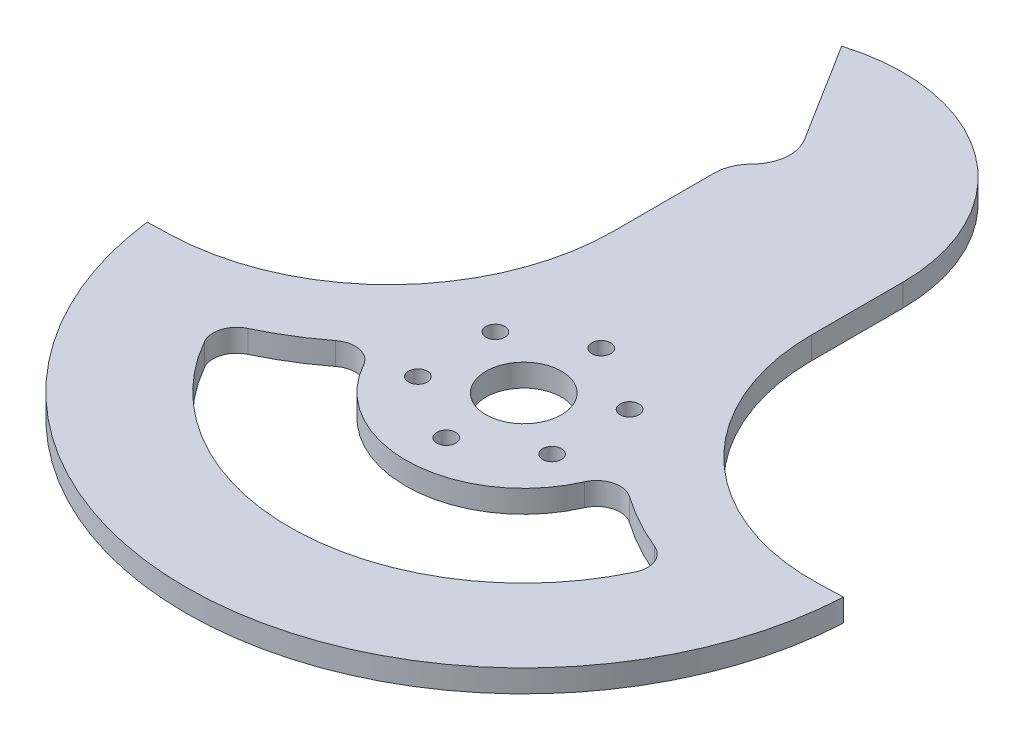
SolidWorks part; units mm, degrees
ref_plane "Front Plane" through (0, 0, 0) normal (0, 0, 1) x (1, 0, 0)
ref_plane "Top Plane" through (0, 0, 0) normal (0, 1, 0) x (1, 0, 0)
ref_plane "Right Plane" through (0, 0, 0) normal (1, 0, 0) x (0, 0, -1)
other "Center of Mass"
sketch "Sketch1" plane through (0, 0, 0) normal (0, 1, 0) x (1, 0, 0)
  line L0 (0, 0) -> (-23040.0357, 36803.9862) construction
  line L1 (0, -1000) -> (0, 49000) construction
  line L2 (-29.7853, 97.136) -> (-16.5198, 75.9457)
  line L3 (18.7342, 112.0138) -> (41531.855, 12841.4067) construction
  line L4 (-20, 60.3286) -> (20, 60.3286) construction
  line L5 (-20, 60.3286) -> (-20, 39.1549)
  line L6 (20, 60.3286) -> (20, 40.9875)
  line L7 (0, 0) -> (-71.0663, -8.7258) construction
  line L8 (0, 0) -> (71.5019, -3.7473) construction
  line L9 (-71.0663, -8.7258) -> (71.5019, -3.7473) construction
  line L10 (-71.0663, -8.7258) -> (-66.0694, -8.5513)
  line L11 (71.5019, -3.7473) -> (66.5049, -3.9218)
  line L12 (-28.8426, 54.8122) -> (35326.4965, 35410.1512) construction
  circle A0 centre (0, 0) radius 101.6 construction
  arc A1 (-16.5198, 75.9457) -> (-17.6481, 66.0067) centre (-23.3262, 71.6848) cw
  arc A2 (-17.6481, 66.0067) -> (-20, 60.3286) centre (-11.97, 60.3286) ccw
  arc A3 (-29.7853, 97.136) -> (20, 60.3286) centre (-18.4989, 60.3286) cw
  circle A4 centre (0, 0) radius 71.6 construction
  arc A5 (-71.0663, -8.7258) -> (71.5019, -3.7473) centre (0, 0) ccw
  arc A6 (-66.0694, -8.5513) -> (-20, 39.1549) centre (-67.7353, 39.1549) ccw
  arc A7 (20, 40.9875) -> (66.5049, -3.9218) centre (64.9367, 40.9875) ccw
  circle A8 centre (0, 0) radius 30.5026 construction
  point P9 (0, 60.3286)
  point P20 (0, -71.6)
  point P21 (0, -101.6)
  point P31 (2.4988, -71.5564)
  point P34 (-15.2961, 71.6848)
  dimension "D1" = 203.2
  dimension "D2" = 75
  dimension "D3" = 25
  dimension "D4" = 40
  dimension "D5" = 30
  dimension "D6" = 92
  dimension "D7" = 170
  dimension "D8" = 5
  dimension "D9" = 45
extrude "Boss-Extrude1" add sketch "Sketch1" along normal blind 4.7625
sketch "Sketch6" plane through (0, 4.7625, 0) normal (0, 1, 0) x (1, 0, 0)
  line L0 (-41.0794, -17.6358) -> (-47.4528, -4.0572) construction
  line L1 (29.2213, -7.1458) -> (38.1596, 4.9002) construction
  arc A0 (-45.5884, -19.5412) -> (46.8909, -16.168) centre (0, 0) ccw
  arc A1 (-16.623, 2.7783) -> (-45.5884, -19.5412) centre (-67.7353, 39.1549) cw
  arc A2 (14.252, 8.9958) -> (46.8909, -16.168) centre (64.9367, 40.9875) ccw
  arc A3 (-16.623, 2.7783) -> (14.252, 8.9958) centre (0, 0) ccw
  arc A4 (-66.0694, -8.5513) -> (-20, 39.1549) centre (-67.7353, 39.1549) ccw construction
  arc A5 (-71.0663, -8.7258) -> (71.5019, -3.7473) centre (0, 0) ccw construction
  arc A6 (20, 40.9875) -> (66.5049, -3.9218) centre (64.9367, 40.9875) ccw construction
  circle A7 centre (0, 0) radius 30.5026 construction
  point P23 (0, -49.6)
  dimension "D1" = 22
  dimension "D2" = 15
extrude "Cut-Extrude2" cut sketch "Sketch6" against normal through all
fillet "Fillet6" radius 5 2 edges at (46.8909, 2.3813, 16.168) (-45.5884, 2.3813, 19.5412)
sketch "Sketch7" plane through (0, 4.7625, 0) normal (0, 1, 0) x (1, 0, 0)
  circle A0 centre (0, 0) radius 25
  dimension "D1" = 50
extrude "Boss-Extrude5" add sketch "Sketch7" against normal up to surface (4.7625 mm away) up to face at (0.9289, 0, 19.6333)
fillet "Fillet7" radius 5 2 edges at (24.7558, 2.3813, 3.486) (-24.2527, 2.3813, 6.0666)
sketch "Sketch8" plane through (0, 4.7625, 0) normal (0, 1, 0) x (1, 0, 0)
  circle A0 centre (0.1682, -0.1726) radius 8
  dimension "D1" = 16
extrude "Cut-Extrude3" cut sketch "Sketch8" against normal through all
sketch "Sketch10" plane through (0, 4.7625, 0) normal (0, 1, 0) x (1, 0, 0)
  circle A0 centre (0.1682, -16.5859) radius 8.4133 construction
  circle A1 centre (0, 0) radius 25 construction
  circle A2 centre (0.1682, -0.1726) radius 8 construction
  circle A3 centre (0.1682, -16.5859) radius 2
  circle A4 centre (-14.0462, -8.3792) radius 2
  circle A5 centre (-14.0462, 8.0341) radius 2
  circle A6 centre (0.1682, 16.2407) radius 2
  circle A7 centre (14.3825, 8.0341) radius 2
  circle A8 centre (14.3825, -8.3792) radius 2
  point P21 (0.1682, -0.1726)
  dimension "D1" = 4
  dimension "D2" = 6
extrude "Cut-Extrude4" cut sketch "Sketch10" against normal through all
sketch "Sketch11" plane through (0, 0, 0) normal (0, 1, 0) x (1, 0, 0)
  circle A0 centre (0.1682, -0.1726) radius 101.8143 construction
  circle A1 centre (0.1682, -0.1726) radius 8 construction
  circle A2 centre (0.1682, -0.1726) radius 71.7461 construction
ref_axis "Axis1" through (0.1682, 0, 0.1726) along (0, 1, 0)
